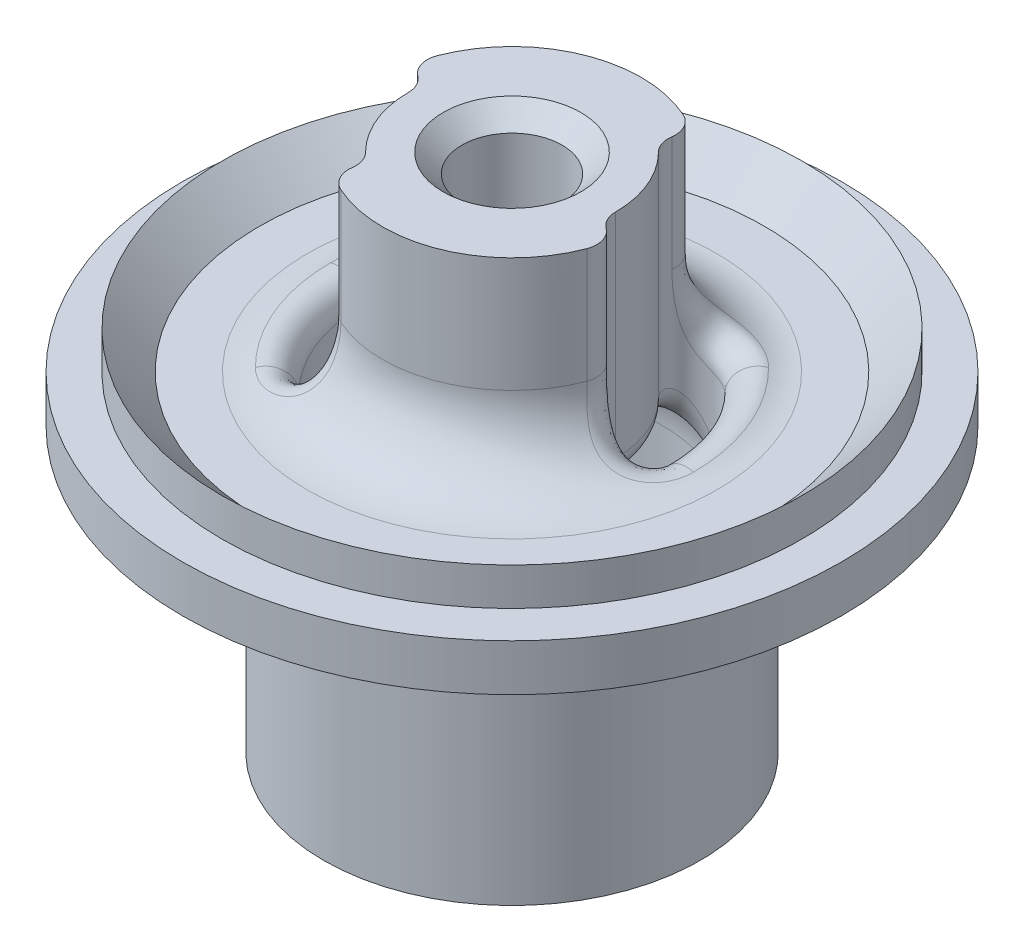
SolidWorks part; units mm, degrees
material "6061-T6 (SS)"
ref_plane "Front Plane" through (0, 0, 0) normal (0, 0, 1) x (1, 0, 0)
ref_plane "Top Plane" through (0, 0, 0) normal (0, 1, 0) x (1, 0, 0)
ref_plane "Right Plane" through (0, 0, 0) normal (1, 0, 0) x (0, 0, -1)
sketch "Sketch1" plane through (0, 0, 0) normal (0, 1, 0) x (1, 0, 0)
  circle A0 centre (0, 0) radius 22.225
  dimension "D1" = 44.45
extrude "Boss-Extrude1" add sketch "Sketch1" along normal blind 3.1496
sketch "Sketch2" plane through (0, 3.1496, 0) normal (0, 1, 0) x (1, 0, 0)
  circle A0 centre (0, 0) radius 8.7312
  dimension "D1" = 17.4625
extrude "Boss-Extrude2" add sketch "Sketch2" along normal blind 12.827 contours A0
fillet "Fillet1" radius 5.08 1 edges at (0, 3.1496, 8.7312)
sketch "Sketch4" plane through (0, 15.9766, 0) normal (0, 1, 0) x (1, 0, 0)
  circle A0 centre (0, 0) radius 3.3734
  dimension "D1" = 6.7469
extrude "Cut-Extrude1" cut sketch "Sketch4" against normal through all
sketch "Sketch5" plane through (0, 3.1496, 0) normal (0, 1, 0) x (1, 0, 0)
  circle A0 centre (0, 0) radius 19.558
  circle A1 centre (0, 0) radius 22.225 construction
  circle A2 centre (0, 0) radius 17.018
  dimension "D1" = 2.667
  dimension "D2" = 2.54
extrude "Boss-Extrude3" add sketch "Sketch5" along normal blind 2.54
chamfer "Chamfer1" distance 2.54 angle 45 1 edges at (0, 5.6896, 17.018)
sketch "Sketch6" plane through (0, 0, 0) normal (0, -1, 0) x (-1, 0, 0)
  circle A0 centre (0, 0) radius 12.7
  circle A1 centre (0, 0) radius 10.16
  dimension "D1" = 25.4
extrude "Boss-Extrude4" add sketch "Sketch6" along normal blind 19.05
fillet "Fillet2" radius 5.08 1 edges at (0, 0, -10.16)
chamfer "Chamfer2" distance 1.27 angle 45 1 edges at (0, 15.9766, 3.3734)
sketch "Sketch7" plane through (0, -19.05, 0) normal (0, -1, 0) x (1, 0, 0)
  line L0 (0, 0) -> (10.16, 0) construction
  line L1 (0, 0) -> (7.1842, -7.1842) construction
  line L2 (0, 0) -> (-6.9412, 6.9412) construction
  line L3 (0, 0) -> (-8.5725, 0) construction
  arc A0 (4.9391, -4.9391) -> (6.985, 0) centre (0, 0) ccw
  arc A1 (7.1842, -7.1842) -> (10.16, 0) centre (0, 0) ccw
  circle A2 centre (0, 0) radius 8.5725 construction
  arc A3 (10.16, 0) -> (6.985, 0) centre (8.5725, 0) ccw
  arc A4 (4.9391, -4.9391) -> (7.1842, -7.1842) centre (6.0617, -6.0617) ccw
  arc A5 (-10.16, 0) -> (-6.985, 0) centre (-8.5725, 0) ccw
  arc A6 (-4.9391, 4.9391) -> (-7.1842, 7.1842) centre (-6.0617, 6.0617) ccw
  arc A7 (-4.9391, 4.9391) -> (-6.985, 0) centre (0, 0) ccw
  arc A8 (-7.1842, 7.1842) -> (-10.16, 0) centre (0, 0) ccw
  dimension "D1" = 13.97
  dimension "D2" = 20.32
  dimension "D3" = 17.145
  dimension "D4" = 45
  dimension "D5" = 180
extrude "Cut-Extrude2" cut sketch "Sketch7" against normal through all
fillet "Fillet3" radius 1.5875 16 edges at (-4.6313, -1.0603, 6.7503) (-7.9621, -0.9921, -1.4654) (4.6313, -1.0603, -6.7503) (7.9621, -0.9921, 1.4654) (-4.9485, 12.1031, 7.1935) (-5.9832, 5.2322, 7.6472) (-9.3866, 4.6976, 3.8881) (-8.5857, 12.1031, -1.5874) (4.9485, 12.1031, -7.1935) (5.9832, 5.2322, -7.6472) (8.5857, 12.1031, 1.5874) (9.7319, 5.1227, 1.0844) (-6.4533, -0.3707, 2.673) (6.4533, -0.3707, -2.673) (-9.7319, 5.1227, -1.0844) (9.3866, 4.6976, -3.8881)
equation "\"ThrustTHK\"= .125"
equation "\"TapDrill\"= 17 / 64"
equation "\"D1@Sketch4\"=\"TapDrill\""
equation "\"ALTHK\"= .1"
equation "\"D2@Sketch6\"=\"ALTHK\""
equation "\"D3@Sketch7\"=(\"D1@Sketch7\"+\"D2@Sketch7\")/2"
